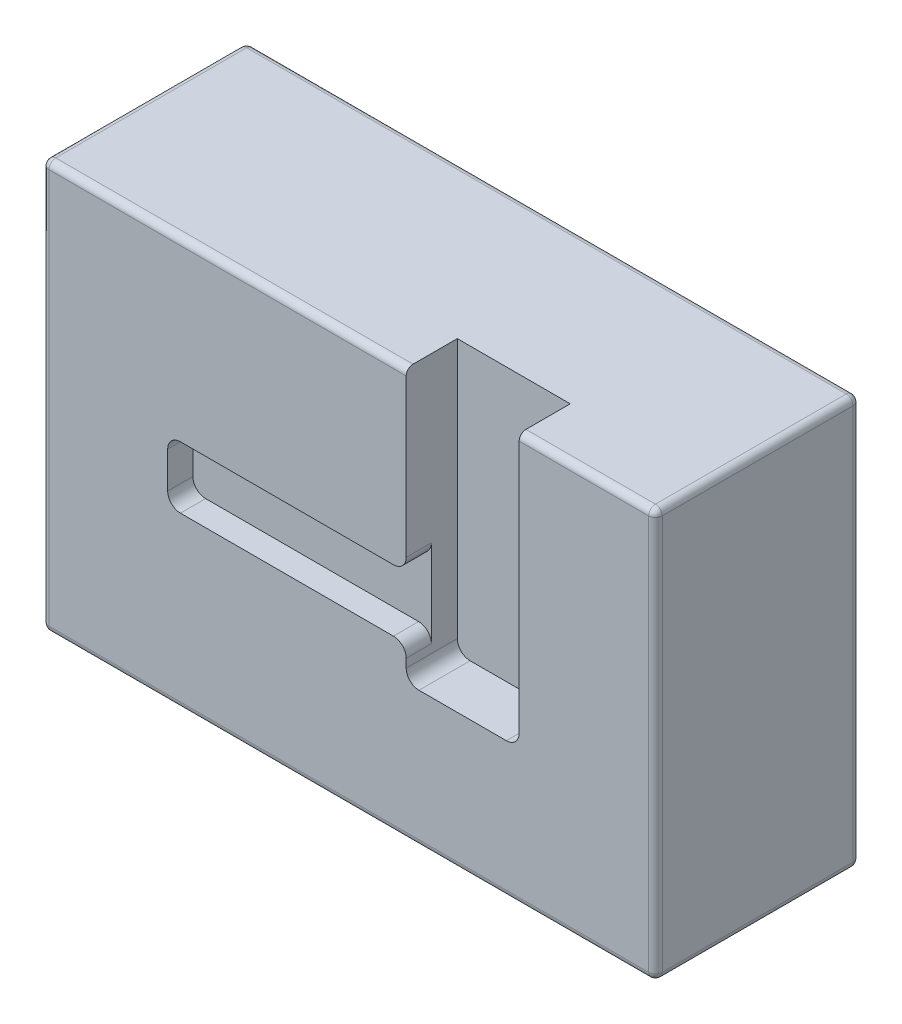
SolidWorks part; units mm, degrees
ref_plane "Alzado" through (0, 0, 0) normal (0, 0, 1) x (1, 0, 0)
ref_plane "Planta" through (0, 0, 0) normal (0, 1, 0) x (1, 0, 0)
ref_plane "Vista lateral" through (0, 0, 0) normal (1, 0, 0) x (0, 0, -1)
sketch "Croquis1" plane through (0, 0, 0) normal (0, 0, 1) x (1, 0, 0)
  line L0 (0, 0) -> (0, 152.4)
  line L1 (0, 152.4) -> (143.7, 152.4)
  line L2 (143.7, 152.4) -> (143.7, 137.35)
  line L3 (143.7, 137.35) -> (228.6, 137.35)
  line L4 (228.6, 137.35) -> (228.6, 0)
  line L5 (228.6, 0) -> (0, 0)
  line L6 (52.8, 152.4) -> (90.9, 152.4)
  line L7 (90.9, 84.55) -> (90.9, 152.4)
  line L8 (52.8, 52.8) -> (52.8, 152.4)
  line L9 (52.8, 52.8) -> (90.9, 52.8)
  line L10 (90.9, 52.8) -> (90.9, 65.5)
  line L11 (90.9, 65.5) -> (179.8, 65.5)
  line L12 (179.8, 65.5) -> (179.8, 84.55)
  line L13 (179.8, 84.55) -> (90.9, 84.55)
  line L14 (90.9, 84.55) -> (90.9, 65.5)
  line L15 (92.9, 50.8) -> (92.9, 65.5)
  line L16 (50.8, 50.8) -> (92.9, 50.8)
  line L17 (50.8, 50.8) -> (50.8, 154.4)
  line L18 (50.8, 154.4) -> (92.9, 154.4)
  line L19 (92.9, 84.55) -> (92.9, 154.4)
  line L20 (90.9, 63.5) -> (181.8, 63.5)
  line L21 (181.8, 63.5) -> (181.8, 86.55)
  line L22 (181.8, 86.55) -> (90.9, 86.55)
  dimension "D2" = 50.8
  dimension "D3" = 50.8
  dimension "D4" = 152.4
  dimension "D5" = 12.7
  dimension "D6" = 38.1
  dimension "D7" = 50.8
  dimension "D8" = 19.05
  dimension "D9" = 88.9
  dimension "D10" = 50.8
  dimension "D13" = 228.6
  dimension "D11" = 2
  dimension "D12" = 2
extrude "Saliente-Extruir1" add sketch "Croquis1" along normal blind 19.05 contours L13 L12 L11 L10 L9 L8 L1 L0 L5 L4 L3 L2 L7 | L12 L13 L7 L1 L8 L9 L10 L11 | L13 L14 L11 L12 | L20 L10 L9 L8 L1 L17 L16 L15 | L22 L19 L1 L7 | L21 L22 L19 L13 L12 L11 L15 L20 | L10 L20 L15 L11 | L19 L22 L7 L13 region at (2.7474, 76.2, 0) region at (51.8, 151.3002, 0) region at (71.85, 102.6, 0) region at (91.9, 119.475, 0) region at (91.9, 85.55, 0) region at (91.9, 64.5, 0) region at (93.8184, 64.5, 0) region at (135.35, 75.025, 0)
extrude "Saliente-Extruir2" add sketch "Croquis1<4>" along normal blind 38.1 contours L13 L12 L11 L10 L9 L8 L1 L0 L5 L4 L3 L2 L7 region at (2.7474, 76.2, 0)
sketch "Croquis1<4>" plane through (0, 0, 0) normal (0, 0, 1) x (1, 0, 0) same geometry as "Croquis1"
extrude "Saliente-Extruir3" add sketch "Croquis1<5>" along normal blind 28.702 contours L13 L14 L11 L12 | L21 L22 L19 L13 L12 L11 L15 L20 region at (93.8184, 64.5, 0) region at (135.35, 75.025, 0)
sketch "Croquis1<5>" plane through (0, 0, 0) normal (0, 0, 1) x (1, 0, 0) same geometry as "Croquis1"
sketch "Croquis2" plane through (0, 0, 38.1) normal (0, 0, 1) x (1, 0, 0)
  line L1 (92.9, 50.8) -> (50.8, 50.8)
  line L2 (92.9, 50.8) -> (92.9, 152.4)
  line L3 (92.9, 152.4) -> (50.8, 152.4)
  line L4 (50.8, 50.8) -> (50.8, 152.4)
extrude "Cortar-Extruir1" cut sketch "Croquis2" against normal up to surface (19.05 mm away) up to face at (81.875, 88.3125, 19.05)
fillet "Redondeo1" radius 4.7625 6 edges at (181.8, 63.5, 33.401) (181.8, 86.55, 33.401) (92.9, 63.5, 33.401) (92.9, 86.55, 33.401) (92.9, 50.8, 28.575) (50.8, 50.8, 28.575)
sketch "Croquis4" plane through (0, 137.35, 0) normal (0, 1, 0) x (1, 0, 0)
  line L1 (143.7, 0) -> (228.6, 0)
  line L2 (143.7, 0) -> (143.7, -38.1)
  line L3 (143.7, -38.1) -> (228.6, -38.1)
  line L4 (228.6, 0) -> (228.6, -38.1)
extrude "Saliente-Extruir4" add sketch "Croquis4" along normal up to surface (15.05 mm away) up to face at (71.85, 152.4, 23.8125)
sketch "Croquis5" plane through (0, 0, 0) normal (0, 0, -1) x (-1, 0, 0)
  line L1 (0, 0) -> (-228.6, 0)
  line L2 (0, 0) -> (0, 152.4)
  line L3 (0, 152.4) -> (-228.6, 152.4)
  line L4 (-228.6, 0) -> (-228.6, 152.4)
extrude "Saliente-Extruir5" add sketch "Croquis5" along normal blind 38.1
fillet "Redondeo2" radius 2.54 13 edges at (114.3, 152.4, -38.1) (114.3, 0, 38.1) (114.3, 0, -38.1) (0, 76.2, 38.1) (0, 0, 0) (0, 76.2, -38.1) (0, 152.4, 0) (228.6, 76.2, 38.1) (228.6, 152.4, 0) (228.6, 76.2, -38.1) (228.6, 0, 0) (160.75, 152.4, 38.1) (25.4, 152.4, 38.1)
sketch "Croquis6" plane through (0, 0, -38.1) normal (0, 0, -1) x (-1, 0, 0)
  line L0 (-2.54, 152.4) -> (-50.8, 152.4) construction
  line L1 (0, 2.54) -> (0, 149.86) construction
  line L2 (-226.06, 0) -> (-2.54, 0) construction
  line L3 (-228.6, 149.86) -> (-228.6, 2.54) construction
  circle A0 centre (-25.4, 127) radius 10
  circle A1 centre (-203.2, 127) radius 10
  circle A2 centre (-203.2, 25.4) radius 10
  circle A3 centre (-25.4, 25.4) radius 10
  circle A6 centre (-114.3, 25.4) radius 10
  point P14 (0, 0)
  dimension "D1" = 20
  dimension "D2" = 25.4
  dimension "D3" = 25.4
  dimension "D4" = 25.4
  dimension "D5" = 25.4
  dimension "D6" = 114.3
extrude "Cortar-Extruir2" cut sketch "Croquis6" against normal blind 71.2
mirror "Simetría1" about plane through (228.6, 0, 19.05) normal (1, 0, 0) of bodies 110
sketch "Croquis7" plane through (0, 0, 38.1) normal (0, 0, 1) x (1, 0, 0)
  line L6 (0, 0) -> (228.6, 0)
  line L7 (0, 0) -> (0, 156.9049)
  line L8 (0, 156.9049) -> (228.6, 156.9049)
  line L9 (228.6, 0) -> (228.6, 156.9049)
  dimension "D1" = 228.6
extrude "Cortar-Extruir3" cut sketch "Croquis7" against normal through all
